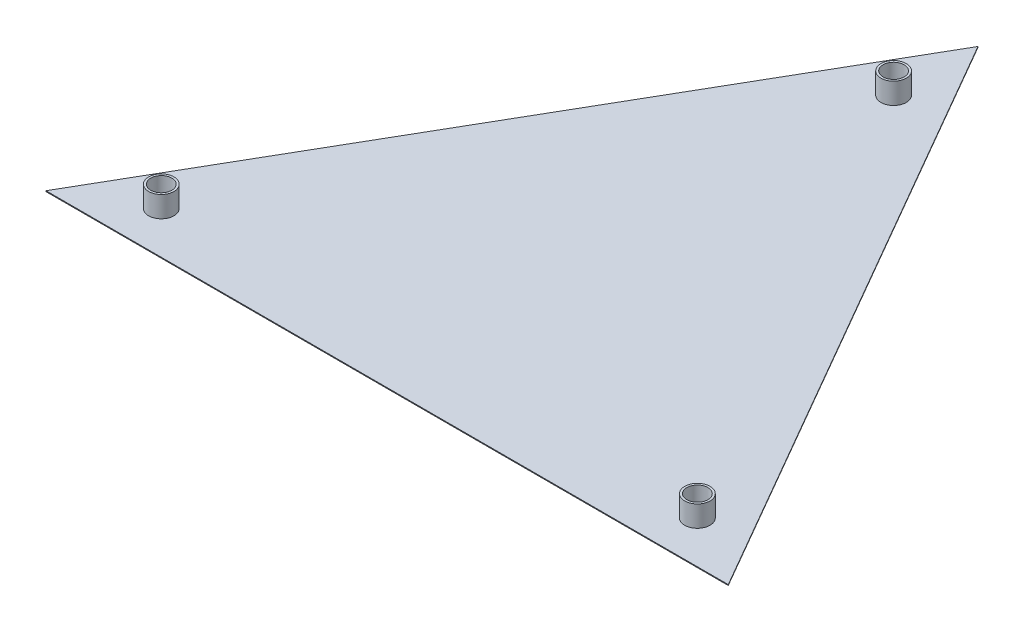
SolidWorks part; units mm, degrees
ref_plane "Front Plane" through (0, 0, 0) normal (0, 0, 1) x (1, 0, 0)
ref_plane "Top Plane" through (0, 0, 0) normal (0, 1, 0) x (1, 0, 0)
ref_plane "Right Plane" through (0, 0, 0) normal (1, 0, 0) x (0, 0, -1)
sketch "Sketch1" plane through (0, 0, 0) normal (0, 1, 0) x (1, 0, 0)
  line L1 (347.2736, 23.6092) -> (347.2736, 3.6092) construction
  line L2 (428.1137, -116.4172) -> (410.7932, -106.4172) construction
  line L10 (266.4391, -116.428) -> (283.7585, -106.4261) construction
  line L57 (266.4391, -116.428) -> (428.1137, -116.4172)
  line L58 (347.2736, 23.6092) -> (428.1137, -116.4172)
  line L59 (266.4391, -116.428) -> (347.2736, 23.6092)
  circle A1 centre (347.2736, 3.6092) radius 2.5
  circle A2 centre (283.7585, -106.4261) radius 2.5
  circle A3 centre (410.7932, -106.4172) radius 2.5
  circle A4 centre (347.2736, 3.6092) radius 3
  circle A5 centre (410.7932, -106.4172) radius 3
  circle A6 centre (283.7585, -106.4261) radius 3
  point P12 (0, 0)
  dimension "D1" = 20
  dimension "D2" = 5
  dimension "D5" = 5
  dimension "D6" = 5
  dimension "D7" = 6
  dimension "D8" = 6
  dimension "D9" = 6
  dimension "D3" = 20
extrude "Boss-Extrude5" add sketch "Sketch1" against normal blind 0.2 contours L59 L57 L58 A6 A5 A4 region at (347.2755, 0, 69.7453)
extrude "Boss-Extrude6" add sketch "Sketch1<21>" along normal blind 5 separate body contours A6 A2 | A5 | A3 | A4 | A1 region at (280.8434, 0, 106.4261)
sketch "Sketch1<21>" plane through (0, 0, 0) normal (0, 1, 0) x (1, 0, 0) same geometry as "Sketch1"
